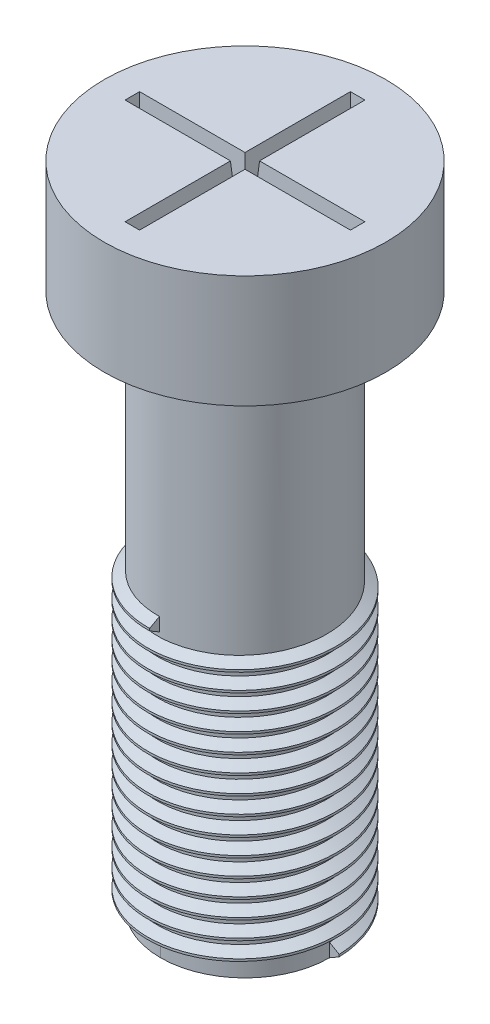
SolidWorks part; units mm, degrees
ref_plane "Front Plane" through (0, 0, 0) normal (0, 0, 1) x (1, 0, 0)
ref_plane "Top Plane" through (0, 0, 0) normal (0, 1, 0) x (1, 0, 0)
ref_plane "Right Plane" through (0, 0, 0) normal (1, 0, 0) x (0, 0, -1)
sketch "Sketch1" plane through (0, 0, 0) normal (0, 0, 1) x (1, 0, 0)
  line L0 (0, 6.5068) -> (0, -9.5473) construction
  line L1 (0, -8.777) -> (-1.5, -8.777)
  line L2 (-1.5, -8.777) -> (-1.5, 0.723)
  line L3 (-1.5, 0.723) -> (-2.5, 0.723)
  line L4 (-2.5, 0.723) -> (-2.5, 2.723)
  line L5 (-2.5, 2.723) -> (0, 2.723)
  line L6 (0, 2.723) -> (0, -8.777)
  dimension "D1" = 1.5
  dimension "D2" = 9.5
  dimension "D3" = 2
  dimension "D4" = 1
revolve "Revolve1" add sketch "Sketch1" angle 360 about L0
sketch "Sketch2" plane through (0, 2.723, 0) normal (0, 1, 0) x (1, 0, 0)
  line L0 (-2, 0.129) -> (-0.129, 0.129)
  line L1 (0.129, -2) -> (-0.129, -2)
  line L2 (0.129, -2) -> (0.129, -0.129)
  line L3 (0.129, 2) -> (-0.129, 2)
  line L4 (-0.129, -2) -> (-0.129, -0.129)
  line L7 (-2, -0.129) -> (-2, 0.129)
  line L8 (-2, -0.129) -> (-0.129, -0.129)
  line L9 (2, -0.129) -> (2, 0.129)
  line L10 (0.129, 2) -> (0.129, 0.129)
  line L11 (-0.129, 2) -> (0.129, 2)
  line L12 (-0.129, 2) -> (-0.129, 0.129)
  line L13 (-0.129, -2) -> (0.129, -2)
  line L14 (2, -0.129) -> (0.129, -0.129)
  line L15 (2, 0.129) -> (2, -0.129)
  line L16 (2, 0.129) -> (0.129, 0.129)
  line L17 (-2, 0.129) -> (-2, -0.129)
  line L18 (-0.129, -0.129) -> (-0.129, -2)
  line L19 (-0.129, 0.129) -> (-0.129, 2)
  line L20 (-0.129, -0.129) -> (-2, -0.129)
  line L23 (0.129, -0.129) -> (0.129, -2)
  line L24 (0.129, -0.129) -> (2, -0.129)
  line L28 (-0.129, 0.129) -> (-2, 0.129)
  line L29 (0.129, 0.129) -> (2, 0.129)
  line L31 (0.129, 0.129) -> (0.129, 2)
  point P0 (0, 0)
  point P21 (0, 0)
  dimension "D1" = 4
  dimension "D2" = 4
extrude "Cut-Extrude1" cut sketch "Sketch2" against normal blind 0.5 draft 4 contours L9 L16 L10 L3 L12 L0 L7 L8 L4 L1 L2 L14 region at (0, 2.723, 0)
thread "Thread1" pitch 0.3175 method extrude profile "Thread Profile1" start angle 0, offset 0, length 5, pitch 0.3175, diameter 3
ref_plane "Plane1" through (1.5, -8.777, 0) normal (0, 0, 1) x (1, 0, 0)
sketch "Thread Profile1" plane through (1.5, -8.777, 0) normal (0, 0, 1) x (1, 0, 0)
  line L0 (0, 0) -> (0, 0.3175) construction
  line L1 (0, 0) -> (0.1719, 0.0992)
  line L2 (0.1719, 0.0992) -> (0.1719, 0.1389)
  line L3 (0.1719, 0.1389) -> (0, 0.2381)
  line L4 (0.1719, 0.1191) -> (0, 0.1191) construction
  line L11 (0, 0) -> (0, 0.2381)
  point P2 (0, 0)
  dimension "Pitch" = 0.3175
  dimension "Profile_Angle" = 60
  dimension "Profile_Land" = 0.0397
  dimension "Profile_Height" = 0.1719
